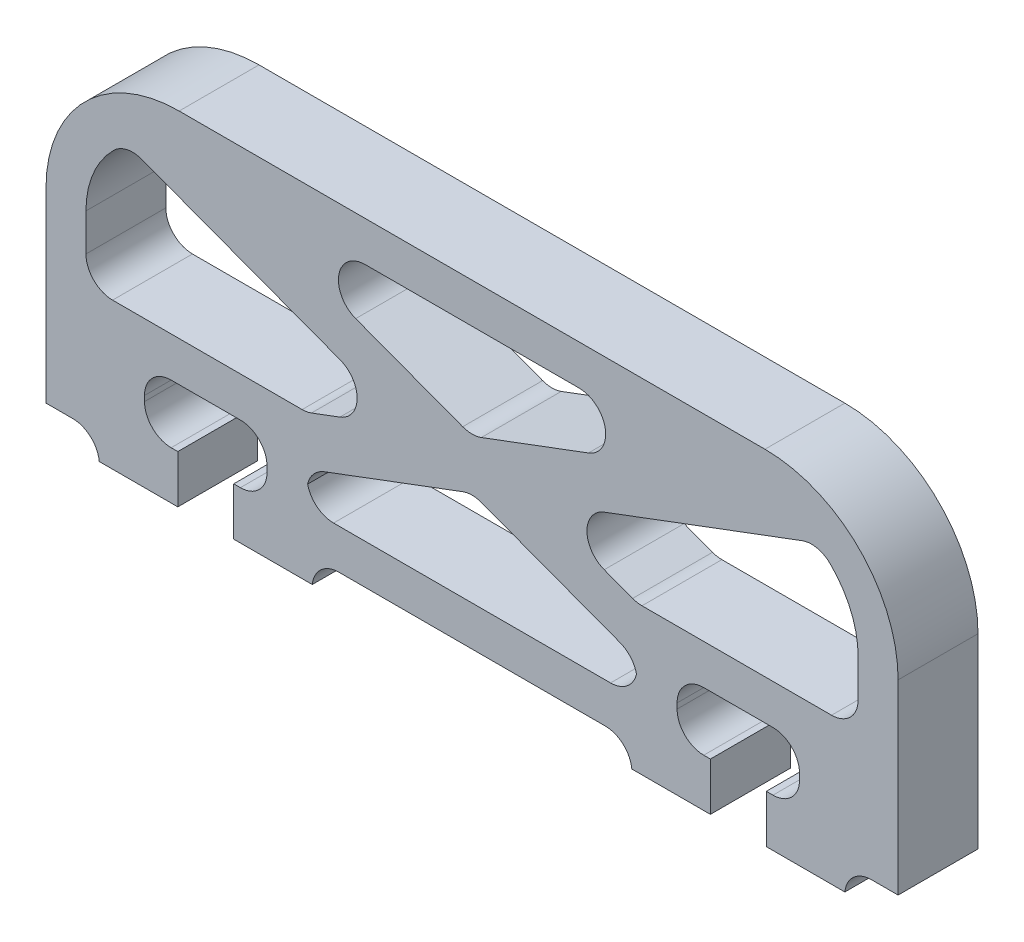
SolidWorks part; units mm, degrees
ref_plane "Front Plane" through (0, 0, 0) normal (0, 0, 1) x (1, 0, 0)
ref_plane "Top Plane" through (0, 0, 0) normal (0, 1, 0) x (1, 0, 0)
ref_plane "Right Plane" through (0, 0, 0) normal (1, 0, 0) x (0, 0, -1)
sketch "Sketch1" plane through (0, 0, 0) normal (0, 0, 1) x (1, 0, 0)
  line L0 (-10, -6.9) -> (-10, 6) construction
  line L1 (-16, 6) -> (16, 6)
  line L2 (-16, 6) -> (-16, -6)
  line L3 (-16, -6) -> (16, -6)
  line L4 (16, 6) -> (16, -6)
  line L5 (-16, 6) -> (16, -6) construction
  line L6 (-16, -6) -> (16, 6) construction
  line L7 (-16, -6) -> (-6, -6)
  line L9 (-14, -6.9) -> (-6, -6.9)
  line L10 (-6, -6) -> (-6, -6.9)
  line L11 (0, 6) -> (0, -6) construction
  line L12 (-11.05, -5.1) -> (-8.95, -5.1)
  line L13 (-11.05, -5.1) -> (-11.05, -6.9)
  line L14 (-11.05, -6.9) -> (-8.95, -6.9)
  line L15 (-8.95, -5.1) -> (-8.95, -6.9)
  line L16 (-11.05, -5.1) -> (-8.95, -6.9) construction
  line L17 (-11.05, -6.9) -> (-8.95, -5.1) construction
  line L18 (-12.3, -2.9) -> (-7.7, -2.9)
  line L19 (-12.3, -2.9) -> (-12.3, -5.1)
  line L20 (-12.3, -5.1) -> (-7.7, -5.1)
  line L21 (-7.7, -2.9) -> (-7.7, -5.1)
  line L22 (-12.3, -2.9) -> (-7.7, -5.1) construction
  line L23 (-12.3, -5.1) -> (-7.7, -2.9) construction
  line L24 (12.3, -2.9) -> (7.7, -2.9)
  line L25 (12.3, -2.9) -> (12.3, -5.1)
  line L26 (12.3, -5.1) -> (7.7, -5.1)
  line L27 (7.7, -2.9) -> (7.7, -5.1)
  line L28 (11.05, -5.1) -> (8.95, -5.1)
  line L29 (11.05, -5.1) -> (11.05, -6.9)
  line L30 (11.05, -6.9) -> (8.95, -6.9)
  line L31 (8.95, -5.1) -> (8.95, -6.9)
  line L32 (16, -6) -> (6, -6)
  line L33 (6, -6) -> (6, -6.9)
  line L34 (14, -6.9) -> (6, -6.9)
  line L36 (-14, -6.9) -> (-14, -6)
  line L37 (14, -6.9) -> (14, -6)
  point P0 (0, 0)
  point P11 (-10, -6)
  point P16 (-10, -4)
  dimension "D1" = 32
  dimension "D2" = 12
  dimension "D3" = 0.9
  dimension "D4" = 8
  dimension "D5" = 2.1
  dimension "D6" = 0.9
  dimension "D7" = 2.2
  dimension "D8" = 4.6
  dimension "D9" = 2
extrude "Base shape" add sketch "Sketch1" along normal blind 3 contours L31 L26 L27 L24 L25 L29 L3 L4 L1 L2 L13 L20 L19 L18 L21 L15 | L3 L15 L9 L10 | L13 L3 L9 | L34 L31 L3 L33 | L3 L29 L34 region at (0, 0.2832, 0) region at (-12.525, -6.45, 0) region at (12.525, -6.45, 0) region at (-7.475, -6.45, 0) region at (7.475, -6.45, 0)
fillet "Edge radiuses" radius 5 2 edges at (16, 6, 1.5) (-16, 6, 1.5)
sketch "Sketch2" plane through (0, 0, 3) normal (0, 0, 1) x (1, 0, 0)
  line L0 (-6, -6) -> (6, -6) construction
  line L1 (16, -6) -> (-16, -6)
  line L2 (16, -6) -> (16, 6)
  line L3 (16, 6) -> (-16, 6)
  line L4 (-16, -6) -> (-16, 6)
  line L5 (16, -6) -> (-16, 6) construction
  line L6 (16, 6) -> (-16, -6) construction
  line L8 (16.3041, -5.189) -> (-15.6959, 6.811)
  line L9 (15.6959, 6.811) -> (-16.3041, -5.189)
  line L10 (15.6959, -6.811) -> (-16.3041, 5.189)
  line L11 (16.3041, 5.189) -> (-15.6959, -6.811)
  line L36 (-16, 1) -> (-16, -6) construction
  line L37 (-13.8, -1.4) -> (-14.5, -1.4)
  line L38 (13.8, -1.4) -> (14.5, -1.4)
  line L60 (11, 4.5) -> (-11, 4.5)
  line L61 (14.5, -4.5) -> (14.5, 1)
  line L62 (-13.8, -1.4) -> (-6.2, -1.4)
  line L63 (-6.2, -1.4) -> (-6.2, -4.5)
  line L64 (-6.2, -4.5) -> (6.2, -4.5)
  line L65 (6.2, -4.5) -> (6.2, -1.4)
  line L66 (6.2, -1.4) -> (13.8, -1.4)
  line L67 (14.5, -4.5) -> (14.5, 1)
  line L68 (11, 4.5) -> (-11, 4.5)
  line L70 (-13.8, -1.4) -> (-6.2, -1.4)
  line L71 (-6.2, -1.4) -> (-6.2, -4.5)
  line L72 (-6.2, -4.5) -> (6.2, -4.5)
  line L73 (6.2, -4.5) -> (6.2, -1.4)
  line L74 (6.2, -1.4) -> (13.8, -1.4)
  line L80 (-14.5, 1) -> (-14.5, -4.5)
  line L81 (-14.5, 1) -> (-14.5, -4.5)
  line L83 (-13.8, -4.5) -> (-13.8, -1.4)
  line L84 (-13.8, -4.5) -> (-13.8, -1.4)
  line L85 (13.8, -1.4) -> (13.8, -4.5)
  line L86 (13.8, -1.4) -> (13.8, -4.5)
  line L87 (13.8, -4.5) -> (14.5, -4.5)
  line L88 (13.8, -4.5) -> (14.5, -4.5)
  line L89 (-14.5, -4.5) -> (-13.8, -4.5)
  line L90 (-14.5, -4.5) -> (-13.8, -4.5)
  arc A4 (14.5, 1) -> (11, 4.5) centre (11, 1) ccw
  arc A5 (14.5, 1) -> (11, 4.5) centre (11, 1) ccw
  arc A8 (-11, 4.5) -> (-14.5, 1) centre (-11, 1) ccw
  arc A9 (-11, 4.5) -> (-14.5, 1) centre (-11, 1) ccw
  point P0 (0, 0)
  dimension "D3" = 1.5
extrude "Inner cuts" cut sketch "Sketch2" against normal up to next contours L10 A9 L81 L90 L9 L84 L70 | L9 L68 L8 | L67 A5 L11 L8 L74 L86 L88 | L72 L73 L10 L11 L71 region at (0, -3.2004, 3) region at (9.9189, 0.6364, 3) region at (-9.9189, 0.6364, 3) region at (0, 3.3083, 3)
fillet "1mm milling radiuses" radius 1 28 edges at (6.2, -4.5, 1.5) (6.2, -3.25, 1.5) (-6.2, -4.5, 1.5) (-6.2, -3.25, 1.5) (0, -0.925, 1.5) (6.2, -1.4, 1.5) (2.4667, 0, 1.5) (9.5333, 4.5, 1.5) (-9.5333, 4.5, 1.5) (0, 0.925, 1.5) (-2.4667, 0, 1.5) (-6.2, -1.4, 1.5) (14.5, -1.4, 1.5) (12.9262, 3.9223, 1.5) (-12.9262, 3.9223, 1.5) (-14.5, -1.4, 1.5) (-7.7, -2.9, 1.5) (-7.7, -5.1, 1.5) (12.3, -5.1, 1.5) (12.3, -2.9, 1.5) (7.7, -2.9, 1.5) (7.7, -5.1, 1.5) (-12.3, -5.1, 1.5) (-12.3, -2.9, 1.5) (14, -6, 1.5) (6, -6, 1.5) (-14, -6, 1.5) (-6, -6, 1.5)
